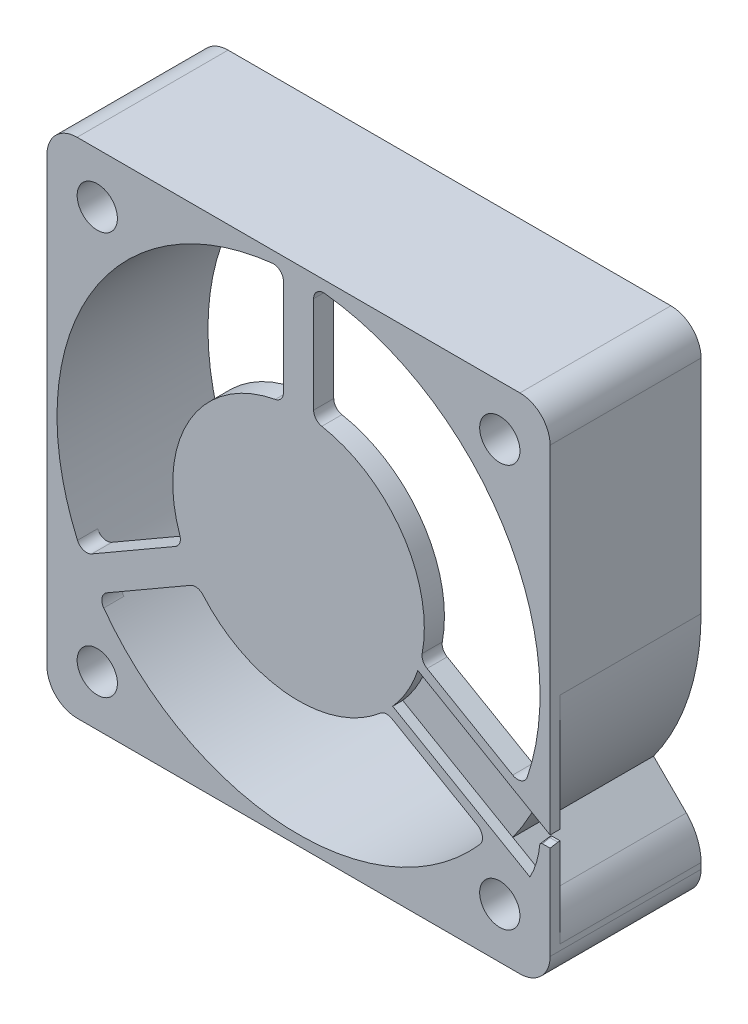
SolidWorks part; units mm, degrees
material "ABS"
ref_plane "Front Plane" through (0, 0, 0) normal (0, 0, 1) x (1, 0, 0)
ref_plane "Top Plane" through (0, 0, 0) normal (0, 1, 0) x (1, 0, 0)
ref_plane "Right Plane" through (0, 0, 0) normal (1, 0, 0) x (0, 0, -1)
sketch "Sketch1" plane through (0, 0, 0) normal (0, 0, 1) x (1, 0, 0)
  line L1 (25, 25) -> (-25, 25)
  line L2 (25, 25) -> (25, -25)
  line L3 (25, -25) -> (-25, -25)
  line L4 (-25, 25) -> (-25, -25)
  line L5 (25, 25) -> (-25, -25) construction
  line L6 (25, -25) -> (-25, 25) construction
  point P0 (0, 0)
  dimension "D1" = 50
  dimension "D2" = 50
extrude "Boss-Extrude1" add sketch "Sketch1" along normal blind 15
fillet "Fillet1" radius 3 4 edges at (-25, -25, 7.5) (25, -25, 7.5) (-25, 25, 7.5) (25, 25, 7.5)
sketch "Sketch3" plane through (0, 0, 0) normal (0, 0, 1) x (1, 0, 0)
  circle A0 centre (0, 0) radius 24
  dimension "D1" = 48
extrude "Cut-Extrude1" cut sketch "Sketch3" along normal blind 13
sketch "Sketch4" plane through (0, 0, 15) normal (0, 0, 1) x (1, 0, 0)
  line L0 (-11.4971, -4.9058) -> (-21.494, -10.6775)
  line L1 (-1.5, 12.4097) -> (1.5, 12.4097)
  line L2 (-1.5, 12.4097) -> (-1.5, 23.9531)
  line L3 (-1.5, 23.9531) -> (1.5, 23.9531)
  line L4 (1.5, 12.4097) -> (1.5, 23.9531)
  line L5 (8.25, 0) -> (-8.25, 0) construction
  line L6 (-22.6102, -13.054) -> (-8.3766, -4.8363) construction
  line L7 (-9.9971, -7.5039) -> (-19.994, -13.2756)
  line L8 (12.1423, -2.9689) -> (22.3124, -8.8406)
  line L9 (8.6423, -9.0311) -> (18.8124, -14.9028)
  line L10 (18.4033, -10.6252) -> (8.7971, -5.079) construction
  circle A0 centre (0, 0) radius 12.5
  circle A1 centre (0, 0) radius 24
  dimension "D1" = 25
  dimension "D2" = 48
  dimension "D3" = 3
  dimension "D4" = 3
  dimension "D5" = 30
  dimension "D6" = 1.5
  dimension "D7" = 7
  dimension "D8" = 3.5
  dimension "D9" = 30
extrude "Cut-Extrude2" cut sketch "Sketch4" against normal blind 13 contours L2 A1 L0 A0 | L7 A1 L4 A0 | L7 A1 L9 A0 region at (-13.9336, 8.0446, 15) region at (-0.876, -16.3875, 15) region at (13.754, 8.9524, 15)
fillet "Fillet2" radius 1 12 edges at (-19.994, -13.2756, 14) (-21.494, -10.6775, 14) (-11.4971, -4.9058, 14) (-9.9971, -7.5039, 14) (-1.5, 23.9531, 14) (1.5, 23.9531, 14) (1.5, 12.4097, 14) (-1.5, 12.4097, 14) (18.8124, -14.9028, 14) (22.3124, -8.8406, 14) (8.6423, -9.0311, 14) (12.1423, -2.9689, 14)
sketch "Sketch5" plane through (0, 0, 15) normal (0, 0, 1) x (1, 0, 0)
  line L0 (11.8566, -3.9587) -> (25, -11.547)
  line L1 (9.3566, -8.2888) -> (23, -16.1658)
  line L2 (12.7727, -3.3329) -> (21.2836, -8.2467) construction
  line L3 (25, -22) -> (25, 22) construction
  line L4 (9.2727, -9.395) -> (17.7836, -14.3088) construction
  line L5 (25, -12.547) -> (24, -12.547)
  circle A0 centre (0, 0) radius 12.5
  arc A1 (23, -16.1658) -> (24, -12.547) centre (15.2062, -12.0645) ccw
  line M29 (25, -22) -> (25, 22)
  dimension "D1" = 25
  dimension "D7" = 8.807
  dimension "D2" = 1
  dimension "D3" = 1
  dimension "D4" = 2
  dimension "D5" = 1
  dimension "D6" = 1
extrude "Cut-Extrude3" cut sketch "Sketch5" against normal blind 1 contours L1 A1 L5 L0 A0 M29 region at (17.3444, -10.0313, 15)
chamfer "Chamfer1" distance 0.762 angle 10 1 edges at (24.5, -12.547, 15) first distance on face at (24.5, -12.547, 14.5)
fillet "Fillet3" radius 0.254 2 edges at (24, -12.547, 14.119) (23.9961, -12.6142, 14.6191)
sketch "Sketch8" plane through (0, 0, 15) normal (0, 0, 1) x (1, 0, 0)
  line L0 (25, -11.547) -> (25, 22) construction
  line L1 (-25, 22) -> (-25, -22) construction
  line L3 (-22, -25) -> (22, -25) construction
  line L4 (22, 25) -> (-22, 25) construction
  circle A0 centre (20, 20) radius 2
  circle A1 centre (-20, 20) radius 2
  circle A2 centre (-20, -20) radius 2
  circle A3 centre (20, -20) radius 2
  dimension "D1" = 4
  dimension "D2" = 5
  dimension "D3" = 5
  dimension "D4" = 5
  dimension "D5" = 5
extrude "Cut-Extrude5" cut sketch "Sketch8" against normal through all
sketch "Sketch9" plane through (0, 0, 0) normal (0, 0, -1) x (-1, 0, 0)
  line L0 (14.6215, 20.2784) -> (18.3431, 24)
  line L1 (20.2784, 14.6215) -> (24, 18.3431)
  line L2 (16.463, 16.463) -> (19.6802, 19.6802) construction
  line L3 (18.3431, 24) -> (7, 24)
  line L4 (-22, 25) -> (22, 25) construction
  line L5 (24, 18.3431) -> (24, 7)
  line L6 (25, 22) -> (25, -22) construction
  line L7 (-14.0126, 15.9531) -> (-17.1122, 19.482) construction
  line L8 (13.6303, -13.6303) -> (17.6777, -17.6777) construction
  line L9 (-19.0195, -19.0195) -> (-13.0911, -13.0911) construction
  line L10 (-18.4187, 24) -> (-14.9428, 20.0427)
  line L11 (-24, 18.2318) -> (-20.5241, 14.2745)
  line L12 (-24, 18.2318) -> (-24, 7)
  line L13 (-18.4187, 24) -> (-7, 24)
  line L14 (-25, -22) -> (-25, 22) construction
  line L15 (24, -18.3431) -> (20.2784, -14.6215)
  line L16 (18.3431, -24) -> (14.6215, -20.2784)
  line L17 (24, -18.3431) -> (24, -7)
  line L18 (18.3431, -24) -> (7, -24)
  line L19 (22, -25) -> (-22, -25) construction
  line L20 (-25, -19.3431) -> (-20.2784, -14.6215)
  line L21 (-18.3431, -24) -> (-14.6215, -20.2784)
  line L22 (-25, -22) -> (-25, 22) construction
  line L23 (-25, -19.3431) -> (-25, 0)
  line L24 (-18.3431, -24) -> (-7, -24)
  circle A0 centre (0, 0) radius 25
  line M15 (-25, 22) -> (-25, -22)
  dimension "D1" = 50
  dimension "D2" = 1
  dimension "D3" = 1
  dimension "D4" = 8
  dimension "D5" = 4
  dimension "D6" = 1
  dimension "D7" = 1
  dimension "D8" = 8
  dimension "D9" = 4
  dimension "D10" = 8
  dimension "D11" = 4
  dimension "D12" = 1
  dimension "D13" = 1
  dimension "D14" = 1
  dimension "D15" = 8
  dimension "D16" = 4
extrude "Cut-Extrude6" cut sketch "Sketch9" against normal blind 8 contours A0 L0 L3 | A0 L5 L1 | A0 L13 L10 | A0 L11 L12 | A0 L15 L17 | A0 L18 L16 | A0 L21 L24 region at (-13.585, 22.8122, 0) region at (-22.8122, 13.585, 0) region at (13.734, 22.741, 0) region at (-22.8122, -13.585, 0) region at (22.8871, 13.4141, 0) region at (-13.585, -22.8122, 0) region at (13.585, -22.8122, 0)
extrude "Cut-Extrude8" cut sketch "Sketch9<4>" against normal blind 14 contours A0 L20 M15 region at (23.5482, -12.7694, 0)
sketch "Sketch9<4>" plane through (0, 0, 0) normal (0, 0, -1) x (-1, 0, 0) same geometry as "Sketch9"
fillet "Fillet5" radius 5 1 edges at (25, -19.3431, 7)
equation "\"D6@Sketch4\"=\"D4@Sketch4\"/2"
equation "\"D8@Sketch4\"=\"D7@Sketch4\"/2"
equation "\"D5@Sketch9\"=\"D4@Sketch9\"/2"
equation "\"D9@Sketch9\"=\"D8@Sketch9\"/2"
equation "\"D11@Sketch9\"=\"D10@Sketch9\"/2"
equation "\"D16@Sketch9\"=\"D15@Sketch9\"/2"
